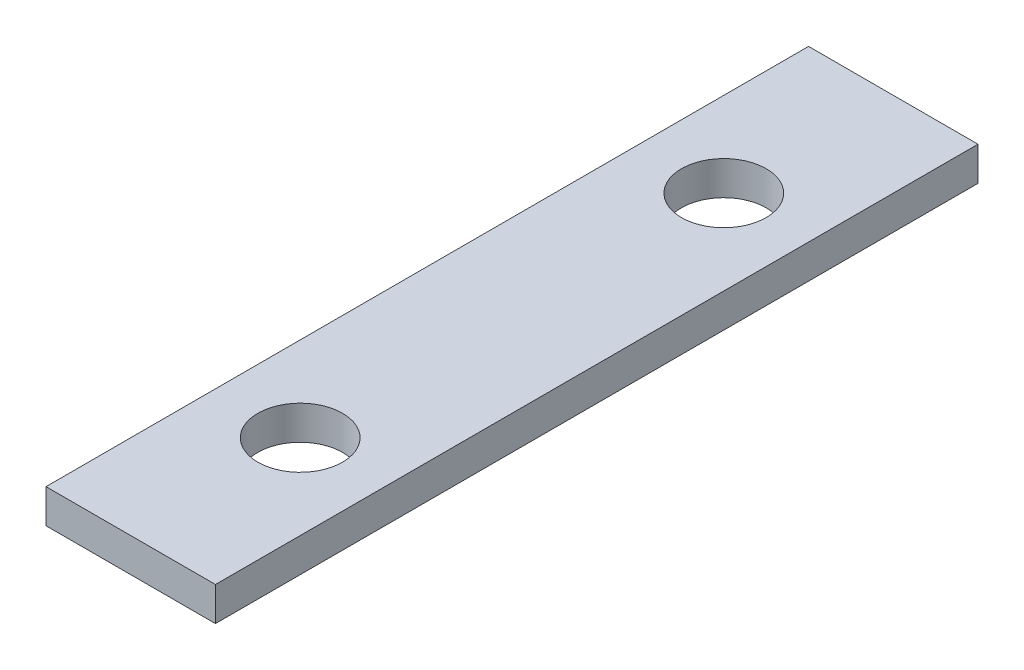
SolidWorks part; units mm, degrees
ref_plane "Спереди" through (0, 0, 0) normal (0, 0, 1) x (1, 0, 0)
ref_plane "Сверху" through (0, 0, 0) normal (0, 1, 0) x (1, 0, 0)
ref_plane "Справа" through (0, 0, 0) normal (1, 0, 0) x (0, 0, -1)
sketch "Эскиз1" plane through (0, 0, 0) normal (0, 1, 0) x (1, 0, 0)
  line L1 (0, 0) -> (20, 0)
  line L2 (0, 0) -> (0, 90)
  line L3 (0, 90) -> (20, 90)
  line L4 (20, 0) -> (20, 90)
  circle A0 centre (10, 20) radius 5
  circle A1 centre (10, 70) radius 5
  dimension "D1" = 2
extrude "Бобышка-Вытянуть1" add sketch "Эскиз1" along normal blind 4
